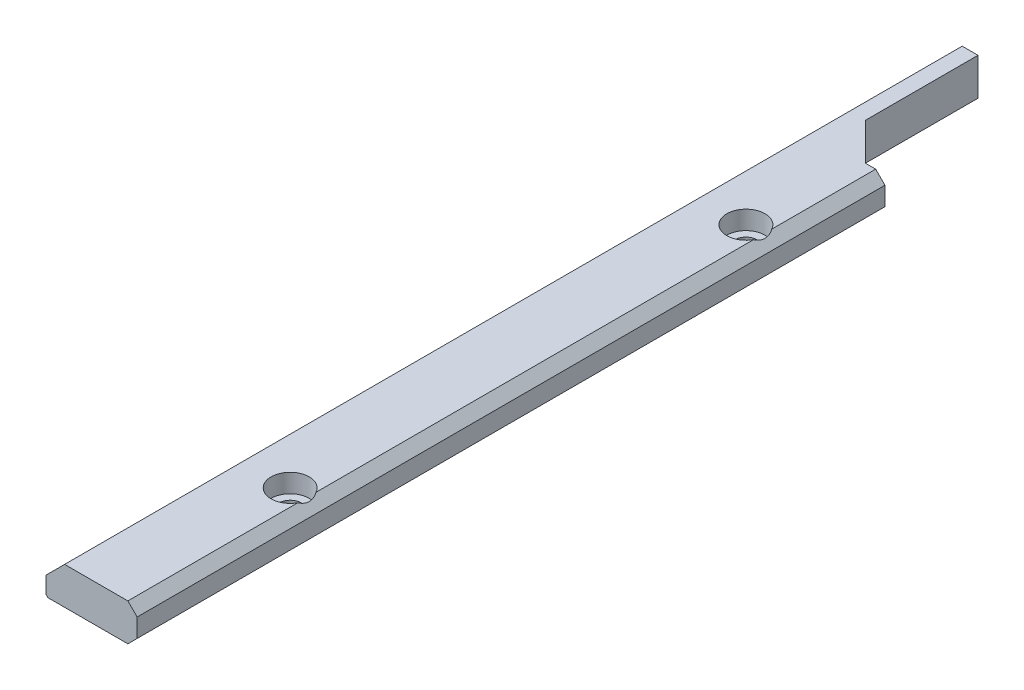
SolidWorks part; units mm, degrees
ref_plane "前视基准面" through (0, 0, 0) normal (0, 0, 1) x (1, 0, 0)
ref_plane "上视基准面" through (0, 0, 0) normal (0, 1, 0) x (1, 0, 0)
ref_plane "右视基准面" through (0, 0, 0) normal (1, 0, 0) x (0, 0, -1)
sketch "草图1" plane through (0, 0, 0) normal (0, 0, 1) x (1, 0, 0)
  line L1 (0, 0) -> (8, 0)
  line L3 (0, 4) -> (8, 4)
  line L4 (8, 0) -> (8, 4)
  line L5 (0, 4) -> (-1.8, 4)
  line L6 (0, 0) -> (0, -1.9)
  line L7 (0, -1.9) -> (-1.8, -1.9)
  line L8 (-1.8, 4) -> (-1.8, -1.9)
  dimension "D1" = 1.8
  dimension "D2" = 1.9
  dimension "D3" = 4
  dimension "D4" = 8
extrude "凸台-拉伸1" add sketch "草图1" against normal blind 96.5
chamfer "倒角1" distance 1 angle 45 1 edges at (8, 0, -48.25)
chamfer "倒角2" distance 1 angle 45 1 edges at (8, 4, -48.25)
sketch "草图2" plane through (0, 4, 0) normal (0, 1, 0) x (1, 0, 0)
  line L0 (5.2, 105.0677) -> (5.2, -16.3861) construction
  line L1 (-1.8, 96.5) -> (-1.8, 0) construction
  line L4 (-28.4042, 48.25) -> (44.7588, 48.25) construction
  line L9 (-1.8, 0) -> (7, 0)
  line L10 (7, 0) -> (7, 96.5)
  line L11 (7, 96.5) -> (-1.8, 96.5)
  line L12 (-1.8, 96.5) -> (-1.8, 0)
  line L13 (-1.8, 0) -> (7, 0) construction
  line L15 (7, 96.5) -> (-1.8, 96.5) construction
  circle A1 centre (5.2, 68.25) radius 2.05
  circle A3 centre (5.2, 19.25) radius 2.05
  circle A4 centre (5.2, 68.25) radius 1.2
  circle A7 centre (5.2, 19.25) radius 1.2
  dimension "D3" = 29
  dimension "D4" = 20
  dimension "D5" = 4.1
  dimension "D6" = 2.4
  dimension "D1" = 0
  dimension "D2" = 7
extrude "切除-拉伸1" cut sketch "草图2" against normal blind 10 and the other way through all contours A7 | A4
extrude "切除-拉伸2" cut sketch "草图2<3>" against normal blind 2 contours A1 | A3
sketch "草图2<3>" plane through (0, 4, 0) normal (0, 1, 0) x (1, 0, 0) same geometry as "草图2"
chamfer "倒角3" distance 2 angle 45 1 edges at (-1.8, 4, -48.25)
sketch "草图3" plane through (0, -1.9, 0) normal (0, -1, 0) x (1, 0, 0)
  line L0 (0, -96.5) -> (0, 0) construction
  line L1 (-1.8, -96.5) -> (0, -96.5)
  line L2 (-1.8, -96.5) -> (-1.8, -89.1)
  line L3 (-1.8, -89.1) -> (0, -89.1)
  line L4 (0, -96.5) -> (0, -89.1)
  line L5 (-1.8, 0) -> (0, 0)
  line L6 (-1.8, 0) -> (-1.8, -7.4)
  line L7 (-1.8, -7.4) -> (0, -7.4)
  line L8 (0, 0) -> (0, -7.4)
  dimension "D1" = 7.4
extrude "切除-拉伸3" cut sketch "草图3" against normal up to surface (1.9 mm away) up to face at (5.2, 0, -20.45)
chamfer "倒角4" distance 0.2 angle 45 8 edges at (0, -0.95, -89.1) (0, -0.95, -7.4) (0, -1.9, -48.25) (-1.8, 0, -92.8) (-1.8, -0.95, -89.1) (-1.8, 0, -3.7) (-1.8, -0.95, -7.4) (-1.8, -1.9, -48.25)
chamfer "倒角5" distance 0.6 angle 45 2 edges at (-0.9, -1.9, -89.1) (-0.9, -1.9, -7.4)
sketch "草图4" plane through (0, 4, 0) normal (0, 1, 0) x (1, 0, 0)
  line L0 (7, 96.5) -> (0.2, 96.5) construction
  line L1 (1.9, 96.5) -> (10.591, 96.5)
  line L2 (1.9, 96.5) -> (1.9, 80.4)
  line L3 (1.9, 80.4) -> (10.591, 80.4)
  line L4 (10.591, 96.5) -> (10.591, 80.4)
  line L5 (8, 96.5) -> (8, 0) construction
  dimension "D1" = 6.1
  dimension "D2" = 16.1
extrude "切除-拉伸4" cut sketch "草图4" against normal through all
sketch "草图5" plane through (0, 4, 0) normal (0, 1, 0) x (1, 0, 0)
  line L0 (1.9, 80.4) -> (5.9, 80.4)
  line L1 (1.9, 80.4) -> (7, 80.4) construction
  line L2 (5.9, 80.4) -> (1.9, 84.4)
  line L3 (1.9, 96.5) -> (1.9, 80.4) construction
  line L4 (1.9, 84.4) -> (1.9, 80.4)
  dimension "D1" = 45
  dimension "D2" = 4
extrude "凸台-拉伸3" add sketch "草图5" against normal blind 1
